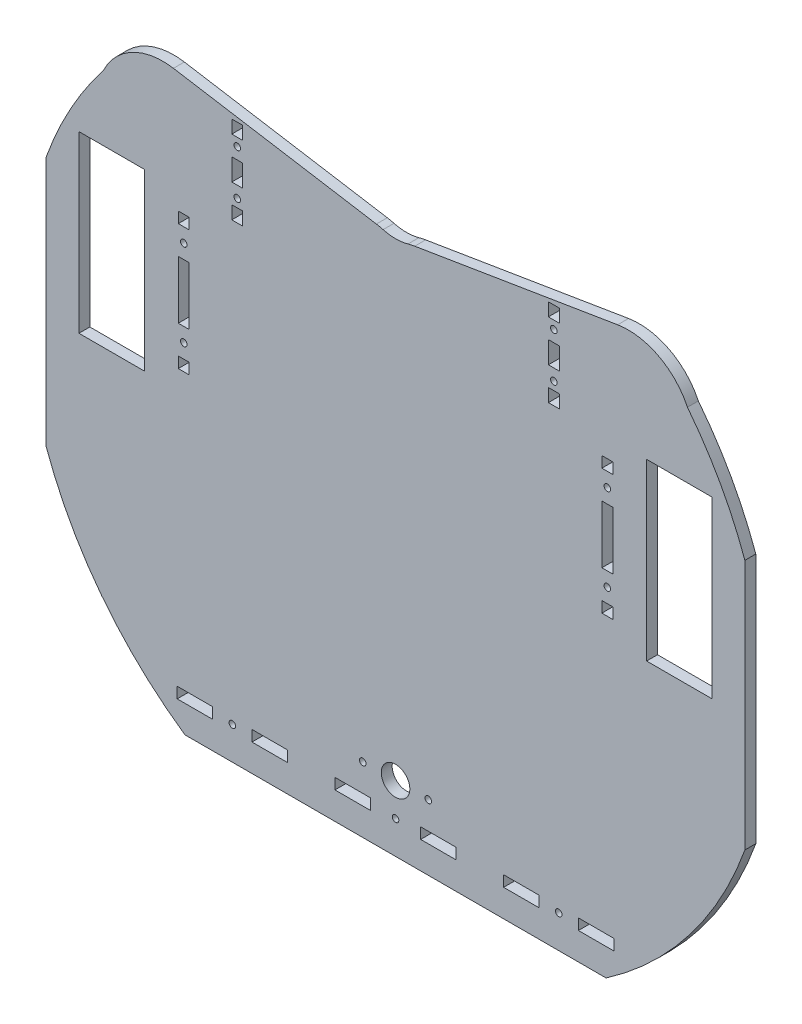
SolidWorks part; units mm, degrees
ref_plane "Front Plane" through (0, 0, 0) normal (0, 0, 1) x (1, 0, 0)
ref_plane "Top Plane" through (0, 0, 0) normal (0, 1, 0) x (1, 0, 0)
ref_plane "Right Plane" through (0, 0, 0) normal (1, 0, 0) x (0, 0, -1)
sketch "Sketch1" plane through (0, 0, 0) normal (0, 0, 1) x (1, 0, 0)
  line L0 (-160, -35) -> (160, -35) construction
  line L1 (133.6974, 70) -> (-133.6974, 70)
  line L2 (160, 22.4456) -> (160, -92.4456)
  line L3 (96.4365, -175) -> (-96.4365, -175)
  line L4 (-160, 22.4456) -> (-160, -92.4456)
  line L5 (0, -175) -> (0, 70) construction
  line L6 (115, -40) -> (145, -40)
  line L7 (-115, 40) -> (-145, 40)
  line L8 (-115, 40) -> (-115, -40)
  line L9 (-115, -40) -> (-145, -40)
  line L10 (-145, 40) -> (-145, -40)
  line L11 (-115, 40) -> (-145, -40) construction
  line L12 (-115, -40) -> (-145, 40) construction
  line L13 (145, 40) -> (145, -40)
  line L14 (115, 40) -> (145, 40)
  line L15 (115, 40) -> (115, -40)
  line L16 (145, 40) -> (115, -40) construction
  line L17 (115, 40) -> (145, -40) construction
  line L18 (-130, 0) -> (130, 0) construction
  arc A0 (-160, -92.4456) -> (-96.4365, -175) centre (0, -35) ccw
  arc A1 (160, 22.4456) -> (133.6974, 70) centre (0, -35) ccw
  arc A3 (96.4365, -175) -> (160, -92.4456) centre (0, -35) ccw
  arc A4 (-160, -92.4456) -> (-96.4365, -175) centre (0, -35) ccw
  arc A5 (-133.6974, 70) -> (-160, 22.4456) centre (0, -35) ccw
  arc A6 (160, 22.4456) -> (133.6974, 70) centre (0, -35) ccw
  arc A7 (96.4365, -175) -> (160, -92.4456) centre (0, -35) ccw
  point P2 (130, 0)
  point P15 (-130, 0)
  point P26 (0, 0)
  point P27 (0, 0)
  dimension "D1" = 30
  dimension "D8" = 340
  dimension "D2" = 15
  dimension "D3" = 260
  dimension "D4" = 30
  dimension "D5" = 80
  dimension "D6" = 35
  dimension "D7" = 5
  dimension "D9" = 140
extrude "Boss-Extrude1" add sketch "Sketch1" along normal blind 5 contours L1 A5 L4 A0 L3 A3 L2 A1 L10 L7 L8 L9 L15 L14 L13 L6 region at (0, -52.0071, 0)
sketch "Sketch2" plane through (0, 0, 5) normal (0, 0, 1) x (1, 0, 0)
  line L0 (-97, 0) -> (-115, 0) construction
  line L1 (-94.5, -31.25) -> (-99.5, -31.25)
  line L2 (-94.5, -31.25) -> (-94.5, 31.25)
  line L3 (-94.5, 31.25) -> (-99.5, 31.25)
  line L4 (-99.5, -31.25) -> (-99.5, 31.25)
  line L5 (-94.5, -31.25) -> (-99.5, 31.25) construction
  line L6 (-94.5, 31.25) -> (-99.5, -31.25) construction
  line L8 (-94.5, 26.25) -> (-99.5, 13.25) construction
  line L9 (-99.5, 26.25) -> (-94.5, 26.25)
  line L10 (-99.5, 26.25) -> (-99.5, 13.25)
  line L11 (-99.5, 13.25) -> (-94.5, 13.25)
  line L12 (-94.5, 26.25) -> (-94.5, 13.25)
  line L13 (-99.5, -13.25) -> (-94.5, -13.25)
  line L14 (-99.5, -13.25) -> (-99.5, -26.25)
  line L15 (-99.5, -26.25) -> (-94.5, -26.25)
  line L16 (-94.5, -13.25) -> (-94.5, -26.25)
  line L17 (-94.5, -13.25) -> (-99.5, -26.25) construction
  line L18 (-97, 19.75) -> (-97, -19.75) construction
  line L19 (-115, 40) -> (-115, -40) construction
  circle A0 centre (-97, 19.75) radius 1.5
  circle A1 centre (-97, -19.75) radius 1.5
  point P0 (-97, 0)
  point P21 (-97, 0)
  dimension "D3" = 3
  dimension "D1" = 5
  dimension "D2" = 18
  dimension "D4" = 62.5
  dimension "D5" = 13
  dimension "D6" = 5
extrude "Cut-Extrude1" cut sketch "Sketch2" against normal blind 5 contours L4 L13 L2 L11 | L4 L9 L2 L3 | L15 L4 L1 L2 | A1 | A0 region at (-97, -28.75, 5) region at (-97, 0, 5) region at (-97, 28.75, 5)
mirror "Mirror1" about plane through (0, 0, 0) normal (1, 0, 0) of "Cut-Extrude1"
sketch "Sketch3" plane through (0, 0, 5) normal (0, 0, 1) x (1, 0, 0)
  line L0 (-6.8891, 71.1336) -> (-133.6974, 92)
  line L2 (-133.6974, 92) -> (-133.6974, 70)
  line L3 (-133.6974, 70) -> (133.6974, 70)
  line L4 (133.6974, 70) -> (133.6974, 92)
  line L5 (133.6974, 92) -> (6.8891, 71.1336)
  line L6 (-133.6974, 92) -> (133.6974, 92) construction
  arc A0 (-6.8891, 71.1336) -> (6.8891, 71.1336) centre (0, 91.5) ccw
  line M20 (133.6974, 70) -> (-133.6974, 70)
  dimension "D2" = 43
  dimension "D1" = 22
extrude "Boss-Extrude2" add sketch "Sketch3" against normal blind 5 contours A0 L0 L2 L3 | A0 L4 L5 M20 region at (-89.2091, 77.3396, 5) region at (89.2091, 77.3396, 5)
fillet "Fillet1" radius 30 4 edges at (-6.8891, 71.1336, 2.5) (6.8891, 71.1336, 2.5) (133.6974, 92, 2.5) (-133.6974, 92, 2.5)
sketch "Sketch4" plane through (0, 0, 5) normal (0, 0, 1) x (1, 0, 0)
  line L1 (-145, -40) -> (-115, -40)
  line L2 (-145, -40) -> (-145, 40)
  line L3 (-145, 40) -> (-115, 40)
  line L4 (-115, -40) -> (-115, 40)
  line L5 (115, -40) -> (145, -40)
  line L6 (115, -40) -> (115, 40)
  line L7 (115, 40) -> (145, 40)
  line L8 (145, -40) -> (145, 40)
extrude "Boss-Extrude3" [suppressed] add sketch "Sketch4" against normal blind 5
sketch "Sketch5" plane through (0, 0, 5) normal (0, 0, 1) x (1, 0, 0)
  line L0 (0, -175) -> (0, -145) construction
  line L1 (96.4365, -175) -> (-96.4365, -175) construction
  line L2 (15, -145) -> (-15, -145) construction
  circle A0 centre (0, -145) radius 6.55
  circle A1 centre (15, -145) radius 1.5
  circle A2 centre (-15, -145) radius 1.5
  point P10 (0, -145)
  dimension "D1" = 13.1
  dimension "D3" = 3
  dimension "D2" = 30
  dimension "D4" = 30
extrude "Cut-Extrude2" cut sketch "Sketch5" against normal blind 5
sketch "Sketch6" plane through (0, 0, 5) normal (0, 0, 1) x (1, 0, 0)
  line L0 (0, -160) -> (0, -175) construction
  line L1 (100, -157.5) -> (83.75, -157.5)
  line L2 (100, -157.5) -> (100, -162.5)
  line L3 (100, -162.5) -> (83.75, -162.5)
  line L4 (-100, -157.5) -> (-100, -162.5)
  line L5 (100, -157.5) -> (-100, -162.5) construction
  line L6 (100, -162.5) -> (-100, -157.5) construction
  line L7 (96.4365, -175) -> (-96.4365, -175) construction
  line L8 (65.75, -157.5) -> (49.5, -157.5)
  line L9 (-100, -162.5) -> (-83.75, -162.5)
  line L10 (-100, -162.5) -> (-100, -157.5)
  line L11 (-100, -157.5) -> (-83.75, -157.5)
  line L12 (-83.75, -162.5) -> (-83.75, -157.5)
  line L13 (100, -162.5) -> (83.75, -162.5)
  line L14 (100, -162.5) -> (100, -157.5)
  line L15 (100, -157.5) -> (83.75, -157.5)
  line L16 (83.75, -162.5) -> (83.75, -157.5)
  line L17 (-65.75, -162.5) -> (-49.5, -162.5)
  line L18 (-65.75, -162.5) -> (-65.75, -157.5)
  line L19 (-65.75, -157.5) -> (-49.5, -157.5)
  line L20 (-49.5, -162.5) -> (-49.5, -157.5)
  line L21 (-27.75, -157.5) -> (-11.5, -157.5)
  line L22 (-27.75, -157.5) -> (-27.75, -162.5)
  line L23 (-27.75, -162.5) -> (-11.5, -162.5)
  line L24 (-11.5, -157.5) -> (-11.5, -162.5)
  line L25 (11.5, -157.5) -> (27.75, -157.5)
  line L26 (11.5, -157.5) -> (11.5, -162.5)
  line L27 (11.5, -162.5) -> (27.75, -162.5)
  line L28 (27.75, -157.5) -> (27.75, -162.5)
  line L29 (49.5, -157.5) -> (65.75, -157.5)
  line L30 (49.5, -157.5) -> (49.5, -162.5)
  line L31 (49.5, -162.5) -> (65.75, -162.5)
  line L32 (65.75, -157.5) -> (65.75, -162.5)
  line L33 (65.75, -162.5) -> (49.5, -162.5)
  line L34 (27.75, -162.5) -> (11.5, -162.5)
  line L35 (27.75, -157.5) -> (11.5, -157.5)
  line L36 (-11.5, -157.5) -> (-27.75, -157.5)
  line L37 (-11.5, -162.5) -> (-27.75, -162.5)
  line L38 (-49.5, -157.5) -> (-65.75, -157.5)
  line L39 (-49.5, -162.5) -> (-65.75, -162.5)
  line L40 (-83.75, -157.5) -> (-100, -157.5)
  line L41 (-83.75, -162.5) -> (-100, -162.5)
  line L42 (83.75, -157.5) -> (65.75, -162.5) construction
  line L43 (65.75, -162.5) -> (65.9323, -162.3551) construction
  line L44 (-83.75, -157.5) -> (-65.75, -162.5) construction
  line L45 (-11.5, -157.5) -> (11.5, -162.5) construction
  circle A0 centre (0, -160) radius 1.5
  circle A1 centre (-74.75, -160) radius 1.5
  circle A2 centre (74.75, -160) radius 1.5
  point P0 (0, -160)
  dimension "D4" = 3
  dimension "D1" = 200
  dimension "D2" = 5
  dimension "D3" = 15
  dimension "D5" = 16.25
  dimension "D6" = 18
  dimension "D7" = 23
  dimension "D8" = 18
extrude "Cut-Extrude3" cut sketch "Sketch6" against normal blind 10 contours L9 L12 L11 L4 | L17 L20 L19 L18 | L24 L21 L22 L23 | L28 L25 L26 L27 | L32 L8 L30 L31 | L16 L3 L2 L1 | A0 | A1 | A2 region at (91.875, -160, 5) region at (-91.875, -160, 5) region at (57.625, -160, 5) region at (-57.625, -160, 5) region at (-19.625, -160, 5) region at (19.625, -160, 5) region at (0, -160, 5) region at (-74.75, -160, 5) region at (74.75, -160, 5)
sketch "Sketch7" plane through (0, 0, 5) normal (0, 0, 1) x (1, 0, 0)
  line L0 (-40, 61) -> (-35, 61) construction
  line L1 (-40, 72.5) -> (-35, 72.5)
  line L2 (-40, 72.5) -> (-40, 46)
  line L3 (-40, 46) -> (-35, 46)
  line L4 (-35, 72.5) -> (-35, 46)
  line L5 (-35, 64) -> (-40, 64) construction
  line L6 (-72.5, 70.25) -> (-72.5, 49.75) construction
  line L7 (-40, 72.5) -> (-35, 72.5)
  line L8 (-40, 72.5) -> (-40, 67)
  line L9 (-40, 67) -> (-35, 67)
  line L10 (-35, 72.5) -> (-35, 67)
  line L11 (-40, 46) -> (-35, 46)
  line L12 (-40, 46) -> (-40, 56)
  line L13 (-40, 56) -> (-35, 56)
  line L14 (-35, 46) -> (-35, 56)
  line L15 (-75, 80) -> (-70, 80)
  line L16 (-75, 80) -> (-75, 40)
  line L17 (-75, 40) -> (-70, 40)
  line L18 (-70, 80) -> (-70, 40)
  line L19 (-75, 60) -> (-70, 60) construction
  line L21 (-75, 55) -> (-70, 55)
  line L22 (-75, 55) -> (-75, 65)
  line L23 (-75, 65) -> (-70, 65)
  line L24 (-70, 55) -> (-70, 65)
  line L25 (-75, 55) -> (-70, 65) construction
  line L26 (-75, 65) -> (-70, 55) construction
  line L27 (-75, 80) -> (-70, 80)
  line L28 (-75, 80) -> (-75, 74)
  line L29 (-75, 74) -> (-70, 74)
  line L30 (-70, 80) -> (-70, 74)
  line L31 (-75, 46) -> (-70, 46)
  line L32 (-75, 46) -> (-75, 40)
  line L33 (-75, 40) -> (-70, 40)
  line L34 (-70, 46) -> (-70, 40)
  circle A0 centre (-37.5, 62.5) radius 1.5
  arc A1 (-5.7015, 70.7698) -> (5.7015, 70.7698) centre (0, 91.5) ccw construction
  circle A2 centre (-72.5, 70.25) radius 1.5
  circle A3 centre (-72.5, 49.75) radius 1.5
  point P0 (-37.5, 65)
  point P11 (0, 70)
  point P28 (-72.5, 60)
  point P31 (-72.5, 60)
  dimension "D2" = 3
  dimension "D9" = 3
  dimension "D1" = 5
  dimension "D3" = 35
  dimension "D4" = 65
  dimension "D5" = 5.5
  dimension "D6" = 5
  dimension "D7" = 10
  dimension "D8" = 3
  dimension "D10" = 5
  dimension "D11" = 40
  dimension "D12" = 10
  dimension "D13" = 20.5
  dimension "D14" = 70
  dimension "D15" = 40
  dimension "D16" = 6
extrude "Cut-Extrude4" cut sketch "Sketch7" against normal blind 10 contours L2 L9 L4 L1 | L13 L2 L3 L4 | L23 L16 L21 L18 | L16 L29 L18 L15 | L31 L16 L17 L18 | A0 | A2 | A3 region at (-37.5, 69.75, 5) region at (-37.5, 51, 5) region at (-72.5, 77, 5) region at (-72.5, 60, 5) region at (-72.5, 43, 5)
mirror "Mirror2" about plane through (0, 0, 0) normal (1, 0, 0) of "Cut-Extrude4"
sketch "Sketch8" plane through (0, 0, 5) normal (0, 0, 1) x (1, 0, 0)
  line L1 (-40.0784, 73.3154) -> (-35, 73.3154)
  line L2 (-40.0784, 73.3154) -> (-40.0784, 46)
  line L3 (-40.0784, 46) -> (-35, 46)
  line L4 (-35, 73.3154) -> (-35, 46)
  line L5 (40, 72.5) -> (35, 72.5)
  line L6 (40, 72.5) -> (40, 46)
  line L7 (40, 46) -> (35, 46)
  line L8 (35, 72.5) -> (35, 46)
extrude "Boss-Extrude4" add sketch "Sketch8" against normal blind 5
